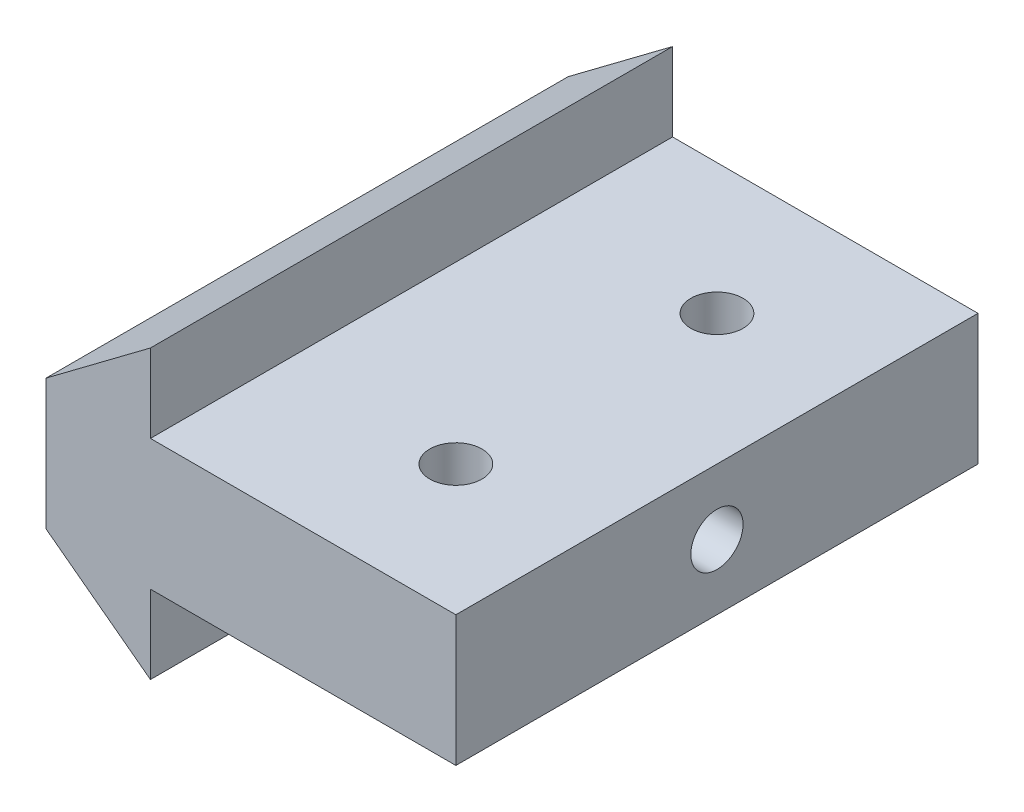
SolidWorks part; units mm, degrees
ref_plane "Plan de face" through (0, 0, 0) normal (0, 0, 1) x (1, 0, 0)
ref_plane "Plan de dessus" through (0, 0, 0) normal (0, 1, 0) x (1, 0, 0)
ref_plane "Plan de droite" through (0, 0, 0) normal (1, 0, 0) x (0, 0, -1)
sketch "ProfileRainureEsquisse" plane through (0, 0, 0) normal (0, 0, 1) x (1, 0, 0)
  line L0 (0, 0) -> (0, 5)
  line L1 (0, 5) -> (4, 8)
  line L2 (0, 0) -> (4, -3)
  line L3 (4, 8) -> (4, 5)
  line L4 (4, 5) -> (15.7, 5)
  line L5 (15.7, 5) -> (15.7, 0)
  line L6 (15.7, 0) -> (4, 0)
  line L7 (4, 0) -> (4, -3)
  dimension "D1" = 4
  dimension "D2" = 15.7
  dimension "D3" = 5
  dimension "D4" = 8
extrude "Boss.-Extru.1" add sketch "ProfileRainureEsquisse" along normal blind 20
sketch "Esquisse3" plane through (0, 0, 0) normal (0, -1, 0) x (1, 0, 0)
  line L0 (15.7, 20) -> (15.7, 0) construction
  line L1 (4, 0) -> (15.7, 0) construction
  line L2 (4, 20) -> (15.7, 20) construction
  circle A0 centre (10.7, 15) radius 1
  circle A1 centre (10.7, 5) radius 1
  dimension "D1" = 2
  dimension "D4" = 2
  dimension "D2" = 5
  dimension "D3" = 5
  dimension "D5" = 5
extrude "Enlèv. mat.-Extru.2" cut sketch "Esquisse3" against normal through all
sketch "Esquisse4" plane through (15.7, 0, 0) normal (1, 0, 0) x (0, 0, -1)
  line L0 (-20, 5) -> (0, 5) construction
  line L1 (-20, 0) -> (0, 0) construction
  circle A0 centre (-10, 2.5) radius 1
  point P2 (-10, 5)
  point P3 (-10, 0)
  dimension "D1" = 2
  dimension "D2" = 2.5
extrude "Enlèv. mat.-Extru.3" cut sketch "Esquisse4" against normal through all
